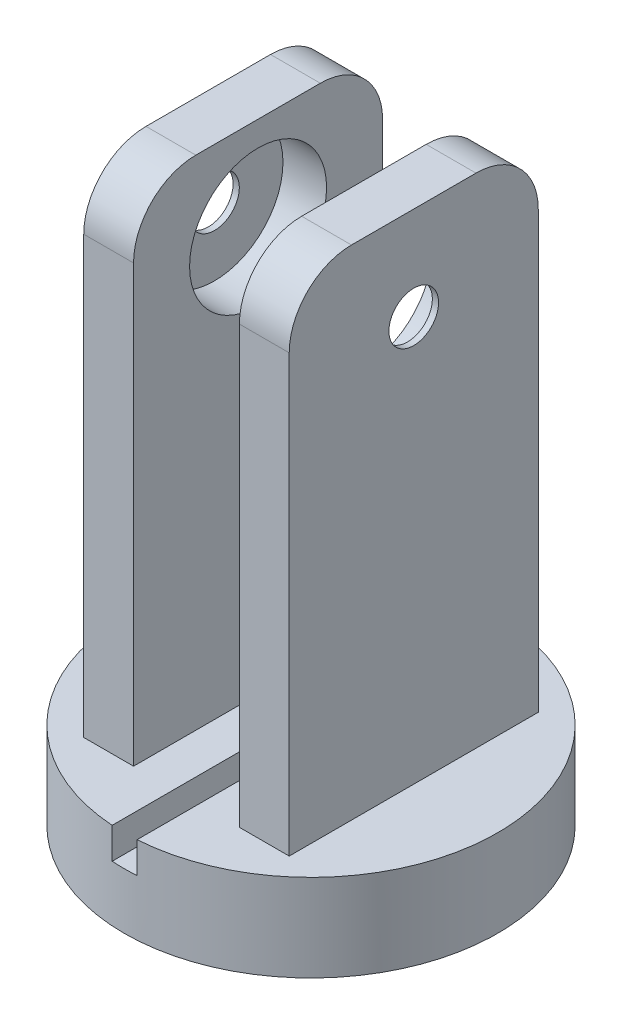
SolidWorks part; units mm, degrees
material "6061 Alloy"
ref_plane "Front Plane" through (0, 0, 0) normal (0, 0, 1) x (1, 0, 0)
ref_plane "Top Plane" through (0, 0, 0) normal (0, 1, 0) x (1, 0, 0)
ref_plane "Right Plane" through (0, 0, 0) normal (1, 0, 0) x (0, 0, -1)
sketch "Sketch1" plane through (0, 0, 0) normal (0, 1, 0) x (1, 0, 0)
  circle A0 centre (0, 0) radius 30
  dimension "D1" = 60
extrude "Boss-Extrude1" add sketch "Sketch1" along normal blind 14
sketch "Sketch2" plane through (0, 0, 0) normal (0, -1, 0) x (1, 0, 0)
  circle A0 centre (0, 0) radius 11.05
  dimension "D1" = 22.1
extrude "Cut-Extrude1" cut sketch "Sketch2" against normal blind 7
sketch "Sketch5" plane through (0, 14, 0) normal (0, 1, 0) x (1, 0, 0)
  line L0 (0, 0) -> (-8.5, 0) construction
  line L1 (0, 0) -> (8.5, 0) construction
  line L2 (-8.5, -20) -> (-8.5, 20)
  line L3 (-8.5, 20) -> (-16.5, 20)
  line L4 (-16.5, 20) -> (-16.5, -20)
  line L5 (-16.5, -20) -> (-8.5, -20)
  line L7 (16.5, -20) -> (16.5, 20)
  line L8 (16.5, 20) -> (8.5, 20)
  line L9 (8.5, 20) -> (8.5, -20)
  line L10 (8.5, -20) -> (16.5, -20)
  dimension "D1" = 8.5
  dimension "D2" = 8.5
  dimension "D3" = 8
  dimension "D4" = 20
  dimension "D5" = 20
  dimension "D6" = 0
  dimension "D7" = 8
  dimension "D8" = 20
  dimension "D9" = 20
extrude "Boss-Extrude2" add sketch "Sketch5" along normal blind 80
fillet "Fillet1" radius 10 4 edges at (-12.5, 94, -20) (12.5, 94, -20) (12.5, 94, 20) (-12.5, 94, 20)
sketch "Sketch8" plane through (0, 14, 0) normal (0, 1, 0) x (1, 0, 0)
  line L0 (0, 0) -> (2, 0) construction
  line L1 (0, 0) -> (-2, 0) construction
  line L2 (2, 29.9333) -> (2, -29.9333)
  line L3 (-2, 29.9333) -> (-2, -29.9333)
  circle A0 centre (0, 0) radius 30 construction
  arc A1 (-2, -29.9333) -> (2, -29.9333) centre (0, 0) ccw
  arc A2 (2, 29.9333) -> (-2, 29.9333) centre (0, 0) ccw
  dimension "D1" = 2
  dimension "D2" = 2
extrude "Cut-Extrude4" cut sketch "Sketch8" against normal blind 5
sketch "Sketch12" plane through (0, 0, 0) normal (1, 0, 0) x (0, 0, -1)
  line L0 (-20, 84) -> (-20, 14) construction
  line L1 (-10, 94) -> (10, 94) construction
  circle A0 centre (0, 79) radius 11
  dimension "D1" = 22
  dimension "D2" = 20
  dimension "D3" = 15
extrude "Cut-Extrude5" cut sketch "Sketch12" against normal offset from surface 1 and the other way offset from surface 1 up to face at (-16.5, 64.6904, 0) other way up to face at (16.5, 64.6904, 0)
sketch "Sketch13" plane through (-16.5, 0, 0) normal (-1, 0, 0) x (0, 0, 1)
  line L0 (-10, 94) -> (10, 94) construction
  line L1 (-20, 84) -> (-20, 14) construction
  circle A0 centre (0, 79) radius 3.99
  dimension "D1" = 7.98
  dimension "D2" = 15
  dimension "D3" = 20
extrude "Cut-Extrude6" cut sketch "Sketch13" against normal up to surface (33 mm away) up to face at (16.5, 64.6904, 0)
